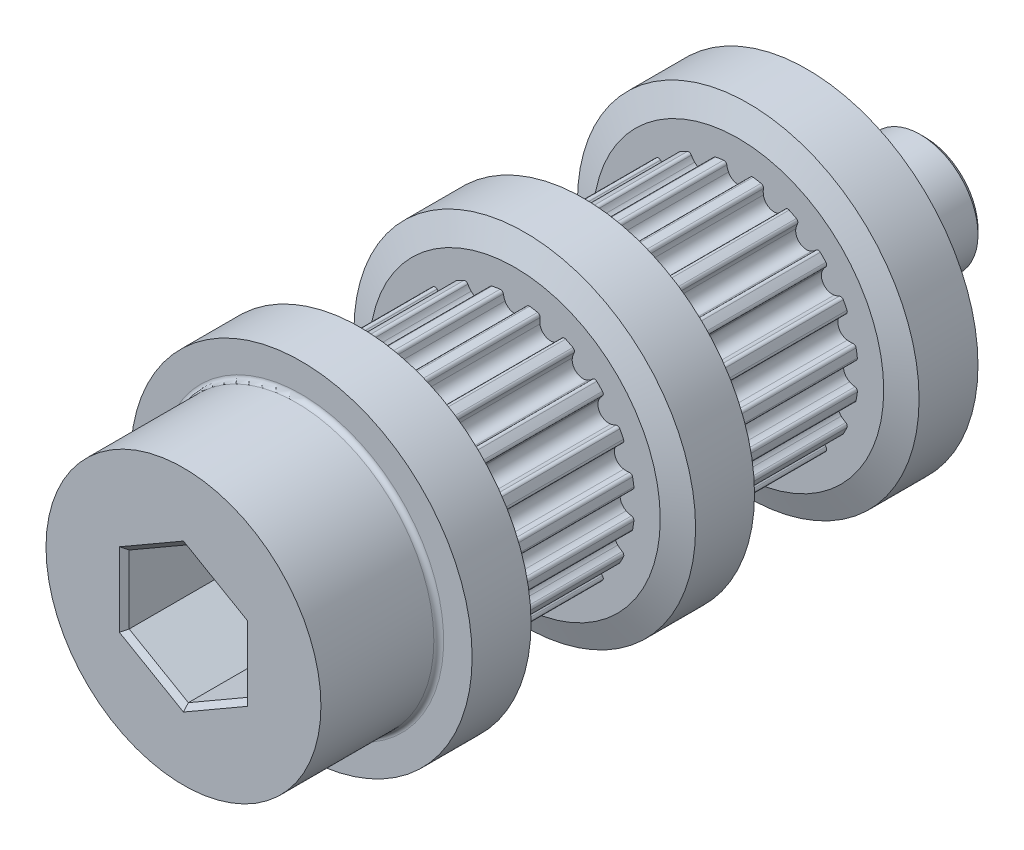
SolidWorks part; units mm, degrees
ref_plane "Front Plane" through (0, 0, 0) normal (0, 0, 1) x (1, 0, 0)
ref_plane "Top Plane" through (0, 0, 0) normal (0, 1, 0) x (1, 0, 0)
ref_plane "Right Plane" through (0, 0, 0) normal (1, 0, 0) x (0, 0, -1)
sketch "Sketch1" plane through (0, 0, 0) normal (0, 0, 1) x (1, 0, 0)
  line B0 (-1.7499, 5.3585) -> (1.7499, 5.3585) construction
  line B1 (0, 0) -> (0, 5.3585) construction
  line B2 (0, 5.3585) -> (0, 11.2111) construction
  line B3 (0, 6.3625) -> (1.9751, 6.0482) construction
  line B4 (1.9751, 6.0482) -> (2.6648, 5.8229) construction
  line B5 (1.9751, 6.0482) -> (1.7499, 5.3585) construction
  line B6 (-1.9751, 6.0482) -> (-1.7499, 5.3585) construction
  line B7 (-1.8963, 5.8067) -> (-2.841, 8.6995)
  line B8 (-2.841, 8.6995) -> (2.841, 8.6995)
  line B9 (2.841, 8.6995) -> (1.8963, 5.8067)
  circle B10 centre (0, 0) radius 6.3625 construction
  circle B11 centre (0, 0) radius 8.6995 construction
  circle B12 centre (0, 0) radius 6.1085 construction
  arc B13 (-0.4989, 5.6703) -> (0.4989, 5.6703) centre (0, 5.9135) ccw
  arc B14 (-0.4989, 5.6703) -> (-0.5855, 5.9387) centre (0.4, 6.1085) cw
  arc B15 (-1.8963, 5.8067) -> (-0.7518, 6.0621) centre (0, 0) cw
  arc B16 (-0.5855, 5.9387) -> (-0.7518, 6.0621) centre (-0.7333, 5.9132) ccw
  arc B17 (1.8963, 5.8067) -> (0.7518, 6.0621) centre (0, 0) ccw
  arc B18 (0.5855, 5.9387) -> (0.7518, 6.0621) centre (0.7333, 5.9132) cw
  arc B19 (0.4989, 5.6703) -> (0.5855, 5.9387) centre (-0.4, 6.1085) ccw
sketch_block_instance "Block-Gt Timing Belt Pulley Groove-1"
sketch_block "Block-Gt Timing Belt Pulley Groove" parameters "D1"=12.725, "D2"=17.399, "D6"=0.555, "D7"=1, "D9"=0.15, "D3"=9.6972, "D4"=4.8486, "D5"=2, "D8"=0.254, "D10"=0.4, "D11"=0.75
sketch "Sketch9" plane through (0, 0, 0) normal (0, 0, 1) x (1, 0, 0)
  line L1 (0, 3.1927) -> (-2.765, 1.5964) construction
  line L2 (-2.765, 1.5964) -> (-2.765, -1.5964) construction
  line L3 (-2.765, -1.5964) -> (0, -3.1927) construction
  line L4 (0, -3.1927) -> (2.765, -1.5964) construction
  line L5 (2.765, -1.5964) -> (2.765, 1.5964) construction
  line L6 (2.765, 1.5964) -> (0, 3.1927) construction
  circle A0 centre (0, 0) radius 2.765 construction
  dimension "D1" = 5.53
sketch "Sketch2" plane through (0, 0, 0) normal (1, 0, 0) x (0, 0, -1)
  line L0 (-3.685, 6.1085) -> (3.685, 6.1085)
  line L1 (-18.57, 0) -> (7.19, 0) construction
  line L2 (-3.685, 6.1085) -> (-3.685, 7.404)
  line L3 (-3.685, 7.404) -> (-4.19, 8.6995)
  line L4 (-4.19, 8.6995) -> (-7.19, 8.6995)
  line L5 (-7.19, 8.6995) -> (-7.695, 7.404)
  line L6 (3.685, 6.1085) -> (3.685, 7.404)
  line L7 (3.685, 7.404) -> (4.19, 8.6995)
  line L8 (4.19, 8.6995) -> (7.19, 8.6995)
  line L9 (7.19, 8.6995) -> (7.19, 0)
  line L10 (0, 6.1085) -> (0, 0) construction
  line L11 (-18.57, 0) -> (7.19, 0)
  line L12 (-7.695, 7.404) -> (-7.695, 6.1085)
  line L13 (-7.695, 6.1085) -> (-15.065, 6.1085)
  line L14 (-15.065, 6.1085) -> (-15.065, 7.404)
  line L15 (-15.065, 7.404) -> (-15.57, 8.6995)
  line L16 (-15.57, 8.6995) -> (-18.57, 8.6995)
  line L17 (-18.57, 8.6995) -> (-18.57, 0)
  dimension "D1" = 12.217
  dimension "D2" = 7.37
  dimension "D3" = 8.38
  dimension "D4" = 17.399
  dimension "D5" = 14.808
  dimension "D6" = 3
revolve "Revolve1" add sketch "Sketch2" angle 360 about L11
sketch "Sketch10" plane through (0, 0, 18.57) normal (0, 0, 1) x (1, 0, 0)
  circle A0 centre (0, 0) radius 7
  dimension "D1" = 14
extrude "Boss-Extrude1" add sketch "Sketch10" along normal blind 6
sketch "Sketch13" plane through (0, 0, -7.19) normal (0, 0, -1) x (-1, 0, 0)
  circle A0 centre (0, 0) radius 2.95
  dimension "D1" = 5.9
extrude "Boss-Extrude2" add sketch "Sketch13" along normal blind 6
sketch "Sketch5" plane through (0, 0, 0) normal (0, 0, 1) x (1, 0, 0)
  line L0 (2.841, 8.6995) -> (1.8963, 5.8067) construction
  line L1 (-1.8963, 5.8067) -> (-2.841, 8.6995) construction
  line L2 (-2.841, 8.6995) -> (2.841, 8.6995) construction
  line L3 (2.841, 8.6995) -> (1.8963, 5.8067)
  line L4 (-1.8963, 5.8067) -> (-2.841, 8.6995)
  line L5 (-2.841, 8.6995) -> (2.841, 8.6995)
  arc A0 (1.8963, 5.8067) -> (0.7518, 6.0621) centre (0, 0) ccw construction
  arc A1 (0.7518, 6.0621) -> (0.5855, 5.9387) centre (0.7333, 5.9132) ccw construction
  arc A2 (0.4989, 5.6703) -> (0.5855, 5.9387) centre (-0.4, 6.1085) ccw construction
  arc A3 (-0.4989, 5.6703) -> (0.4989, 5.6703) centre (0, 5.9135) ccw construction
  arc A4 (-0.5855, 5.9387) -> (-0.4989, 5.6703) centre (0.4, 6.1085) ccw construction
  arc A5 (-0.5855, 5.9387) -> (-0.7518, 6.0621) centre (-0.7333, 5.9132) ccw construction
  arc A6 (-0.7518, 6.0621) -> (-1.8963, 5.8067) centre (0, 0) ccw construction
  arc A7 (1.8963, 5.8067) -> (0.7518, 6.0621) centre (0, 0) ccw
  arc A8 (0.7518, 6.0621) -> (0.5855, 5.9387) centre (0.7333, 5.9132) ccw
  arc A9 (0.4989, 5.6703) -> (0.5855, 5.9387) centre (-0.4, 6.1085) ccw
  arc A10 (-0.4989, 5.6703) -> (0.4989, 5.6703) centre (0, 5.9135) ccw
  arc A11 (-0.5855, 5.9387) -> (-0.4989, 5.6703) centre (0.4, 6.1085) ccw
  arc A12 (-0.5855, 5.9387) -> (-0.7518, 6.0621) centre (-0.7333, 5.9132) ccw
  arc A13 (-0.7518, 6.0621) -> (-1.8963, 5.8067) centre (0, 0) ccw
extrude "Cut-Extrude1" cut sketch "Sketch5" against normal up to surface and the other way up to surface up to face at (6.1085, 0, -3.685) other way up to face at (7.404, 0, 3.685)
sketch "Sketch7" plane through (0, 0, 7.695) normal (0, 0, 1) x (1, 0, 0)
  line L3 (1.8963, 5.8067) -> (2.841, 8.6995)
  line L4 (2.841, 8.6995) -> (-2.841, 8.6995)
  line L5 (-2.841, 8.6995) -> (-1.8963, 5.8067)
  line L6 (1.8963, 5.8067) -> (2.841, 8.6995)
  line L7 (2.841, 8.6995) -> (-2.841, 8.6995)
  line L8 (-2.841, 8.6995) -> (-1.8963, 5.8067)
  arc A7 (-0.7518, 6.0621) -> (-1.8963, 5.8067) centre (0, 0) ccw
  arc A8 (-0.5855, 5.9387) -> (-0.7518, 6.0621) centre (-0.7333, 5.9132) ccw
  arc A9 (-0.5855, 5.9387) -> (-0.4989, 5.6703) centre (0.4, 6.1085) ccw
  arc A10 (-0.4989, 5.6703) -> (0.4989, 5.6703) centre (0, 5.9135) ccw
  arc A11 (0.4989, 5.6703) -> (0.5855, 5.9387) centre (-0.4, 6.1085) ccw
  arc A12 (0.7518, 6.0621) -> (0.5855, 5.9387) centre (0.7333, 5.9132) ccw
  arc A13 (1.8963, 5.8067) -> (0.7518, 6.0621) centre (0, 0) ccw
  arc A14 (-0.7518, 6.0621) -> (-1.8963, 5.8067) centre (0, 0) ccw
  arc A15 (-0.5855, 5.9387) -> (-0.7518, 6.0621) centre (-0.7333, 5.9132) ccw
  arc A16 (-0.5855, 5.9387) -> (-0.4989, 5.6703) centre (0.4, 6.1085) ccw
  arc A17 (-0.4989, 5.6703) -> (0.4989, 5.6703) centre (0, 5.9135) ccw
  arc A18 (0.4989, 5.6703) -> (0.5855, 5.9387) centre (-0.4, 6.1085) ccw
  arc A19 (0.7518, 6.0621) -> (0.5855, 5.9387) centre (0.7333, 5.9132) ccw
  arc A20 (1.8963, 5.8067) -> (0.7518, 6.0621) centre (0, 0) ccw
  dimension "D1" = 0
extrude "Cut-Extrude3" cut sketch "Sketch7" along normal up to surface (7.37 mm away) up to face at (7.404, 0, 15.065)
pattern_circular "CirPattern1" count 20 over 360 about axis through (0, 0, 18.57) along (0, 0, 1) of "Cut-Extrude1", "Cut-Extrude3"
sketch "Sketch11" plane through (0, 0, 18.57) normal (0, 0, 1) x (1, 0, 0)
  line L24 (0, 3.4814) -> (-3.015, 1.7407)
  line L25 (-3.015, 1.7407) -> (-3.015, -1.7407)
  line L26 (-3.015, -1.7407) -> (0, -3.4814)
  line L27 (0, -3.4814) -> (3.015, -1.7407)
  line L28 (3.015, -1.7407) -> (3.015, 1.7407)
  line L29 (3.015, 1.7407) -> (0, 3.4814)
  line L30 (0, 3.4814) -> (-3.015, 1.7407)
  line L31 (-3.015, 1.7407) -> (-3.015, -1.7407)
  line L32 (-3.015, -1.7407) -> (0, -3.4814)
  line L33 (0, -3.4814) -> (3.015, -1.7407)
  line L34 (3.015, -1.7407) -> (3.015, 1.7407)
  line L35 (3.015, 1.7407) -> (0, 3.4814)
  dimension "D1" = 0.25
extrude "Cut-Extrude4" cut sketch "Sketch11" along normal through all
fillet "Fillet1" radius 0.25 2 edges at (7, 0, 18.57) (-2.95, 0, -7.19)
chamfer "Chamfer1" distance 0.25 angle 45 7 edges at (-2.95, 0, -13.19) (-3.015, 0, 24.57) (-1.5075, 2.6111, 24.57) (1.5075, 2.6111, 24.57) (3.015, 0, 24.57) (1.5075, -2.6111, 24.57) (-1.5075, -2.6111, 24.57)
ref_plane "Plane1" through (0, 0, 0) normal (0, 0, 1) x (1, 0, 0)
ref_plane "Plane2" through (0, 0, 11.38) normal (0, 0, 1) x (1, 0, 0)
